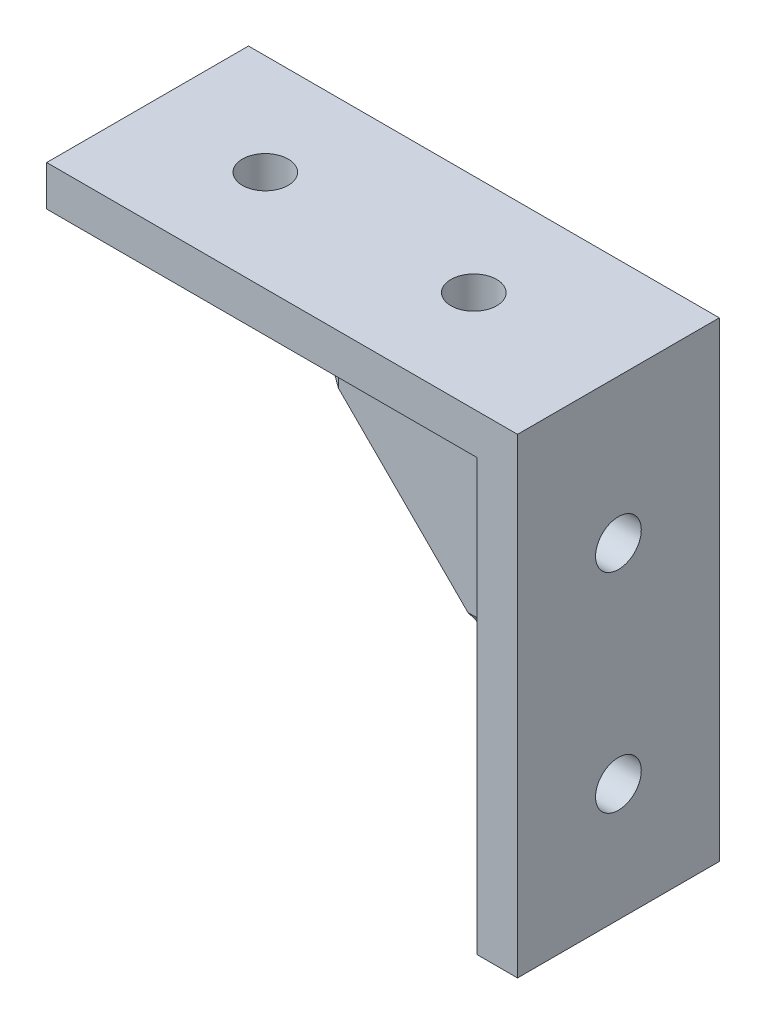
SolidWorks part; units mm, degrees
material "ABS"
ref_plane "Front Plane" through (0, 0, 0) normal (0, 0, 1) x (1, 0, 0)
ref_plane "Top Plane" through (0, 0, 0) normal (0, 1, 0) x (1, 0, 0)
ref_plane "Right Plane" through (0, 0, 0) normal (1, 0, 0) x (0, 0, -1)
ref_plane "Plane4" through (0, 0, 10) normal (0, 0, -1) x (-1, 0, 0)
sketch "Sketch1" plane through (0, 0, 10) normal (0, 0, -1) x (-1, 0, 0)
  line L0 (-25, -35) -> (10, -35)
  line L1 (10, -35) -> (10, -4)
  line L2 (10, -4) -> (-25, -4)
  line L3 (-25, -4) -> (-25, -35)
  dimension "D1" = 35
  dimension "D2" = 31
extrude "Boss-Extrude1" add sketch "Sketch1" against normal blind 15
sketch "Sketch2" plane through (0, 0, 10) normal (0, 0, -1) x (-1, 0, 0)
  line L0 (10, -4) -> (-21, -35)
  line L1 (-21, -35) -> (10, -35)
  line L2 (10, -35) -> (10, -4)
  line L3 (-25, -4) -> (-25, -35) construction
  line L4 (-25, -35) -> (10, -35) construction
  dimension "D1" = 4
  dimension "D2" = 35
  dimension "D3" = 31
extrude "Cut-Extrude1" cut sketch "Sketch2" against normal blind 4
sketch "Sketch3" plane through (0, -4, 0) normal (0, 1, 0) x (-1, 0, 0)
  line L0 (10, 10) -> (-25, 10)
  line L1 (-25, 10) -> (-25, 25)
  line L2 (-25, 25) -> (10, 25)
  line L3 (10, 25) -> (10, 10)
  line L4 (10, 25) -> (10, 14) construction
  line L5 (10, 10) -> (-25, 10) construction
  dimension "D1" = 35
  dimension "D2" = 15
extrude "Boss-Extrude2" add sketch "Sketch3" along normal blind 4
sketch "Sketch4" plane through (-10, 0, 0) normal (-1, 0, 0) x (0, 0, 1)
  line L0 (25, -35) -> (25, -4)
  line L1 (25, -4) -> (14, -4)
  line L2 (14, -4) -> (14, -35)
  line L3 (14, -35) -> (25, -35)
  line L4 (25, -35) -> (25, 0) construction
  line L5 (25, -35) -> (14, -35) construction
  dimension "D1" = 11
  dimension "D2" = 31
extrude "Cut-Extrude2" cut sketch "Sketch4" against normal blind 31
sketch "Sketch5" plane through (0, -4, 0) normal (0, -1, 0) x (1, 0, 0)
  line L0 (21, 25) -> (-10, 25) construction
  line L1 (-10, 25) -> (-10, 14) construction
  circle A0 centre (-1.25, 17.5) radius 1.7
  circle A1 centre (14.25, 17.5) radius 1.7
  dimension "D1" = 7.5
  dimension "D2" = 15.5
  dimension "D3" = 8.75
  dimension "D4" = 7.5
extrude "Cut-Extrude3" cut sketch "Sketch5" against normal through all
sketch "Sketch6" plane through (21, 0, 0) normal (-1, 0, 0) x (0, 0, 1)
  line L0 (25, -35) -> (25, -4) construction
  line L1 (14, -35) -> (25, -35) construction
  circle A0 centre (17.5, -10.75) radius 1.7
  circle A1 centre (17.5, -26.25) radius 1.7
  dimension "D2" = 15.5
  dimension "D1" = 7.5
  dimension "D3" = 8.75
  dimension "D4" = 7.5
extrude "Cut-Extrude4" cut sketch "Sketch6" against normal through all
sketch "Sketch7" plane through (21, 0, 0) normal (-1, 0, 0) x (0, 0, 1)
  circle A0 centre (17.5, -10.75) radius 4
extrude "Cut-Extrude5" cut sketch "Sketch7" along normal through all
sketch "Sketch8" plane through (21, 0, 0) normal (-1, 0, 0) x (0, 0, 1)
  circle A0 centre (17.5, -26.25) radius 4
extrude "Cut-Extrude6" cut sketch "Sketch8" along normal through all
sketch "Sketch9" plane through (0, -4, 0) normal (0, -1, 0) x (1, 0, 0)
  circle A0 centre (-1.25, 17.5) radius 4
  circle A1 centre (14.25, 17.5) radius 4
extrude "Cut-Extrude7" cut sketch "Sketch9" along normal through all
chamfer "Chamfer1" distance 1 angle 45 1 edges at (5.5, -4, 25)
chamfer "Chamfer2" distance 1 angle 45 1 edges at (21, -19, 25)
